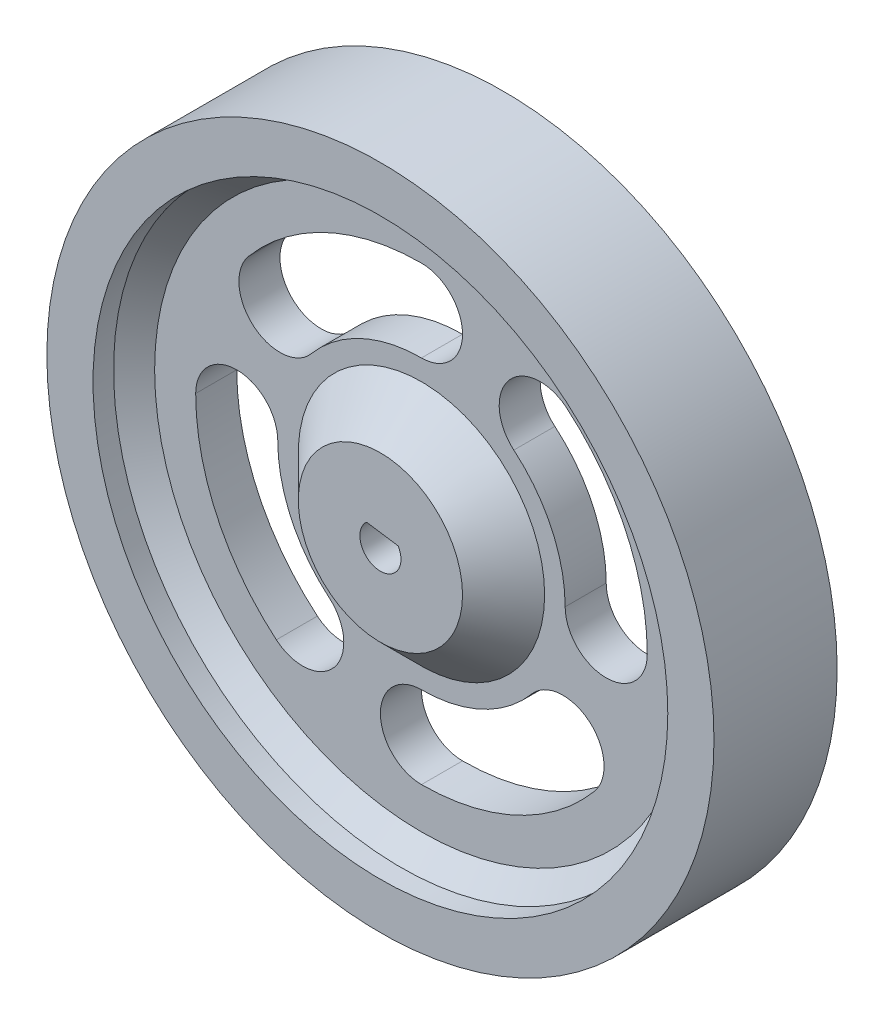
SolidWorks part; units mm, degrees
ref_plane "Plan de face" through (0, 0, 0) normal (0, 0, 1) x (1, 0, 0)
ref_plane "Plan de dessus" through (0, 0, 0) normal (0, 1, 0) x (1, 0, 0)
ref_plane "Plan de droite" through (0, 0, 0) normal (1, 0, 0) x (0, 0, -1)
sketch "Esquisse1" plane through (0, 0, 0) normal (0, 0, 1) x (1, 0, 0)
  line L0 (-1.3545, 1.4715) -> (1.7321, 0.9998)
  line L1 (0, 14) -> (0, 22) construction
  line L3 (-16.853, 14.1413) -> (-10.7246, 8.999) construction
  circle A0 centre (0, 0) radius 32.5
  circle A1 centre (0, 0) radius 2 construction
  arc A2 (-1.3545, 1.4715) -> (1.7321, 0.9998) centre (0, 0) ccw
  circle A3 centre (0, 0) radius 14 construction
  circle A4 centre (0, 0) radius 22 construction
  arc A5 (-10.7246, 8.999) -> (0, 14) centre (0, 0) cw
  arc A6 (0, 22) -> (-16.853, 14.1413) centre (0, 0) ccw
  arc A7 (-16.853, 14.1413) -> (-10.7246, 8.999) centre (-13.7888, 11.5702) ccw
  arc A8 (0, 22) -> (0, 14) centre (0, 18) cw
  arc A9 (22, 0) -> (14.1413, 16.853) centre (0, 0) ccw
  arc A10 (8.999, 10.7246) -> (14, 0) centre (0, 0) cw
  arc A11 (14.1413, 16.853) -> (8.999, 10.7246) centre (11.5702, 13.7888) ccw
  arc A12 (22, 0) -> (14, 0) centre (18, 0) cw
  arc A13 (0, -22) -> (16.853, -14.1413) centre (0, 0) ccw
  arc A14 (10.7246, -8.999) -> (0, -14) centre (0, 0) cw
  arc A15 (16.853, -14.1413) -> (10.7246, -8.999) centre (13.7888, -11.5702) ccw
  arc A16 (0, -22) -> (0, -14) centre (0, -18) cw
  arc A17 (-22, 0) -> (-14.1413, -16.853) centre (0, 0) ccw
  arc A18 (-8.999, -10.7246) -> (-14, 0) centre (0, 0) cw
  arc A19 (-14.1413, -16.853) -> (-8.999, -10.7246) centre (-11.5702, -13.7888) ccw
  arc A20 (-22, 0) -> (-14, 0) centre (-18, 0) cw
  dimension "D1" = 1.25
  dimension "D2" = 4
  dimension "D3" = 50
  dimension "D4" = 4
extrude "Boss.-Extru.1" add sketch "Esquisse1" along normal blind 12
sketch "Esquisse2" plane through (0, 0, 12) normal (0, 0, 1) x (1, 0, 0)
  circle A0 centre (0, 0) radius 28
  circle A1 centre (0, 0) radius 8
extrude "Enlèv. mat.-Extru.1" cut sketch "Esquisse2" against normal blind 4
chamfer "Chanfrein1" distance 4 angle 45 1 edges at (8, 0, 8)
chamfer "Chanfrein2" distance 2 angle 45 1 edges at (28, 0, 8)
ref_plane "Plan1" through (0, 0, 6) normal (0, 0, 1) x (1, 0, 0)
mirror "Symétrie1" about plane through (0, 0, 6) normal (0, 0, 1) of "Chanfrein2", "Enlèv. mat.-Extru.1", "Chanfrein1"
